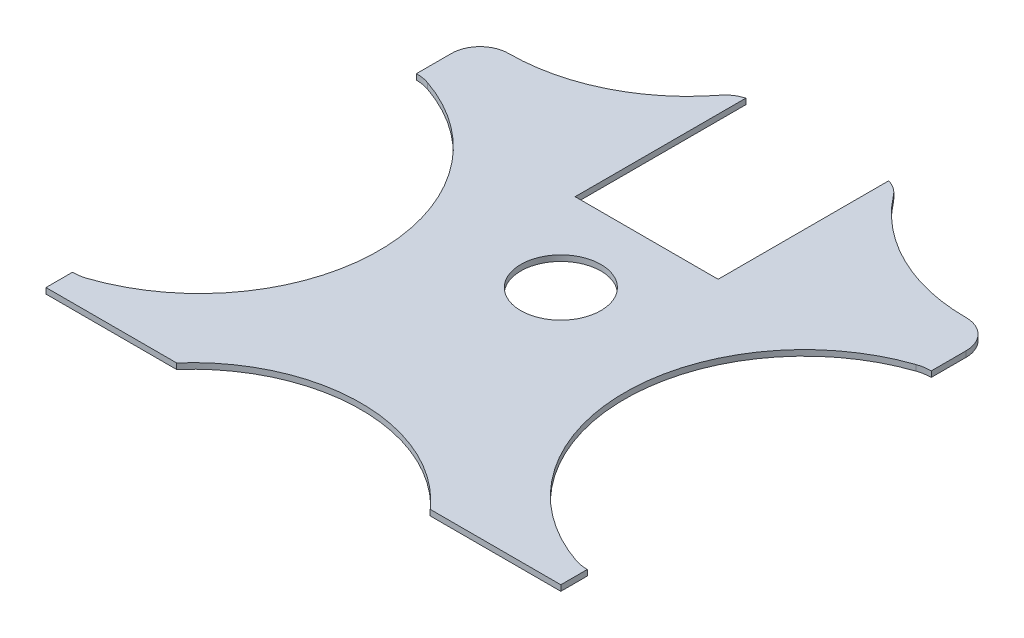
SolidWorks part; units mm, degrees
ref_plane "Front Plane" through (0, 0, 0) normal (0, 0, 1) x (1, 0, 0)
ref_plane "Top Plane" through (0, 0, 0) normal (0, 1, 0) x (1, 0, 0)
ref_plane "Right Plane" through (0, 0, 0) normal (1, 0, 0) x (0, 0, -1)
sketch "Sketch1" plane through (0, 0, 0) normal (0, 1, 0) x (1, 0, 0)
  line L1 (-90, -90) -> (90, -90)
  line L2 (-90, -90) -> (-90, 90)
  line L3 (-90, 90) -> (90, 90)
  line L4 (90, -90) -> (90, 90)
  line L5 (-90, -90) -> (90, 90) construction
  line L6 (-90, 90) -> (90, -90) construction
  point P0 (0, 0)
  dimension "D1" = 180
  dimension "D2" = 180
extrude "Boss-Extrude1" add sketch "Sketch1" along normal blind 2
sketch "Sketch2" plane through (0, 2, 0) normal (0, 1, 0) x (-1, 0, 0)
  line L0 (-90, 90) -> (-90, -90) construction
  line L5 (-90, -90) -> (90, -90) construction
  line L6 (90, -90) -> (90, 90) construction
  line L7 (22.4352, -90) -> (-22.2833, -90) construction
  line L8 (-22.2833, -90) -> (-90, -90)
  line L10 (90, -51.7417) -> (90, -90)
  line L11 (90, -90) -> (22.4352, -90)
  line L12 (-90, -90) -> (-90, -51.7418)
  line L13 (0.0759, -90) -> (0, 0) construction
  circle A0 centre (0, 0) radius 14
  arc A1 (30.3487, -86.1136) -> (79.9966, -61.7417) centre (79.975, -124.4523) cw
  arc A2 (-30.1969, -86.1136) -> (-79.9757, -61.7417) centre (-79.8232, -124.4522) ccw
  arc A3 (-90, -51.7418) -> (-79.9757, -61.7417) centre (-80, -51.7418) ccw
  arc A4 (-30.1969, -86.1136) -> (-22.2833, -90) centre (-22.2833, -80) ccw
  arc A5 (22.4352, -90) -> (30.3487, -86.1136) centre (22.4352, -80) ccw
  arc A6 (79.9966, -61.7417) -> (90, -51.7417) centre (80, -51.7417) ccw
  point P29 (-27.4241, -90)
  point P32 (27.5759, -90)
  point P35 (90, -62.5482)
  dimension "D1" = 28
  dimension "D4" = 10
  dimension "D3" = 55
sketch "Sketch4" plane through (0, 2, 0) normal (0, 1, 0) x (1, 0, 0)
  line L1 (25, 30) -> (-25, 30)
  line L2 (25, 30) -> (25, 90)
  line L3 (25, 90) -> (-25, 90)
  line L4 (-25, 30) -> (-25, 90)
  line L5 (25, 30) -> (-25, 90) construction
  line L6 (25, 90) -> (-25, 30) construction
  point P0 (0, 60)
  dimension "D1" = 60
  dimension "D2" = 50
extrude "Cut-Extrude2" cut sketch "Sketch4" against normal blind 2
sketch "Sketch5" plane through (0, 2, 0) normal (0, 1, 0) x (-1, 0, 0)
  line L0 (90, -90) -> (90, 90) construction
  line L1 (90, -90) -> (90, 90) construction
  line L2 (94.6311, -11.7256) -> (94.6311, 52.9589)
  arc A0 (90, -25.2406) -> (90, 66.4739) centre (105.7136, 20.6167) cw construction
  arc A1 (85.3689, 79.9889) -> (85.3689, -38.7556) centre (105.7136, 20.6167) ccw
  arc A3 (94.6311, 52.9589) -> (85.3689, 79.9889) centre (90, 66.4739) ccw
  arc A4 (85.3689, -38.7556) -> (94.6311, -11.7256) centre (90, -25.2406) ccw
  point P3 (57.2388, 20.6167)
  dimension "D3" = 48.4748
  dimension "D1" = 28.5728
  dimension "D2" = 142.171
extrude "Cut-Extrude3" cut sketch "Sketch5" against normal blind 10
mirror "Mirror2" about plane through (0, 0, 0) normal (1, 0, 0) of "Cut-Extrude3"
sketch "Sketch6" plane through (0, 2, 0) normal (0, 1, 0) x (1, 0, 0)
  line L0 (-90, -90) -> (90, -90) construction
  arc A0 (-44.3381, -90) -> (44.3381, -90) centre (0, -128.8639) cw
extrude "Cut-Extrude4" cut sketch "Sketch6" against normal through all and the other way through all flip side to cut
sketch "Sketch7" plane through (0, 2, 0) normal (0, 1, 0) x (-1, 0, 0)
  arc A0 (90, -51.7417) -> (47.1296, -71.0313) centre (78.2096, -82.8217) ccw
  arc A1 (79.9966, -61.7417) -> (30.3487, -86.1136) centre (79.975, -124.4523) ccw construction
extrude "Cut-Extrude5" cut sketch "Sketch7" against normal through all and the other way through all rebuild error yes
mirror "Mirror3" about plane through (0, 0, 0) normal (1, 0, 0) rebuild error yes
sketch "Sketch8" plane through (0, 2, 0) normal (0, 1, 0) x (-1, 0, 0)
  line L0 (43.4514, 42.5078) -> (43.4514, 42.6843)
  line L1 (53.4514, 52.5078) -> (-53.4514, 52.5078)
  line L2 (53.4514, 52.5078) -> (53.4514, -52.5078)
  line L3 (53.4514, -52.5078) -> (-53.4514, -52.5078)
  line L4 (-53.4514, 52.5078) -> (-53.4514, -52.5078)
  line L5 (53.4514, 52.5078) -> (-53.4514, -52.5078) construction
  line L6 (53.4514, -52.5078) -> (-53.4514, 52.5078) construction
  line L7 (8.6685, -42.5078) -> (-8.6685, -42.5078)
  line L8 (-43.4514, 42.5078) -> (-43.4514, 42.6843)
  line L9 (8.6685, 42.5078) -> (-8.6685, 42.5078)
  line L10 (-43.4514, 10.4007) -> (-43.4514, -10.4007)
  line L11 (-43.4514, -42.6843) -> (-43.4514, -42.5078)
  line L14 (-5.7067, -20.0778) -> (-14.3752, -28.9013)
  line L16 (-19.5266, 5.6065) -> (-29.7447, 16.0072)
  line L17 (-43.4514, 42.5078) -> (-43.4514, -42.5078) construction
  line L18 (-19.5266, -5.6065) -> (-29.7447, -16.0072)
  line L20 (-5.7067, 20.0778) -> (-14.3752, 28.9013)
  line L21 (29.7447, 16.0072) -> (19.5266, 5.6065)
  line L22 (14.3752, -28.9013) -> (5.7067, -20.0778)
  line L23 (43.4514, -42.5078) -> (-43.4514, -42.5078) construction
  line L24 (29.7447, -16.0072) -> (19.5266, -5.6065)
  line L25 (43.4514, -42.6843) -> (43.4514, -42.5078)
  line L26 (43.4514, 42.5078) -> (43.4514, -42.5078) construction
  line L27 (43.4514, 42.5078) -> (-43.4514, 42.5078) construction
  line L28 (43.4514, 10.4007) -> (43.4514, -10.4007)
  line L29 (14.3752, 28.9013) -> (5.7067, 20.0778)
  arc A0 (-5.7067, 20.0778) -> (5.7067, 20.0778) centre (0, 25.6843) ccw
  arc A1 (-14.3752, 28.9013) -> (-8.6685, 42.5078) centre (-8.6685, 34.5078) cw
  arc A2 (8.6685, 42.5078) -> (14.3752, 28.9013) centre (8.6685, 34.5078) cw
  arc A3 (43.4514, 10.4007) -> (29.7447, 16.0072) centre (35.4514, 10.4007) ccw
  arc A4 (19.5266, 5.6065) -> (19.5266, -5.6065) centre (25.2333, 0) ccw
  arc A5 (29.7447, -16.0072) -> (43.4514, -10.4007) centre (35.4514, -10.4007) ccw
  arc A6 (-19.5266, -5.6065) -> (-19.5266, 5.6065) centre (-25.2333, 0) ccw
  arc A7 (-29.7447, 16.0072) -> (-43.4514, 10.4007) centre (-35.4514, 10.4007) ccw
  arc A8 (-43.4514, -10.4007) -> (-29.7447, -16.0072) centre (-35.4514, -10.4007) ccw
  arc A9 (5.7067, -20.0778) -> (-5.7067, -20.0778) centre (0, -25.6843) ccw
  arc A10 (-14.3752, -28.9013) -> (-8.6685, -42.5078) centre (-8.6685, -34.5078) ccw
  arc A11 (14.3752, -28.9013) -> (8.6685, -42.5078) centre (8.6685, -34.5078) cw
  circle A12 centre (0, 0) radius 14
  point P0 (0, 0)
  point P34 (43.4514, 29.959)
  dimension "D2" = 8
  dimension "D1" = 10
extrude "Boss-Extrude2" [suppressed] add sketch "Sketch8" along normal blind 3
extrude "Cut-Extrude6" cut sketch "Sketch2" against normal blind 3
